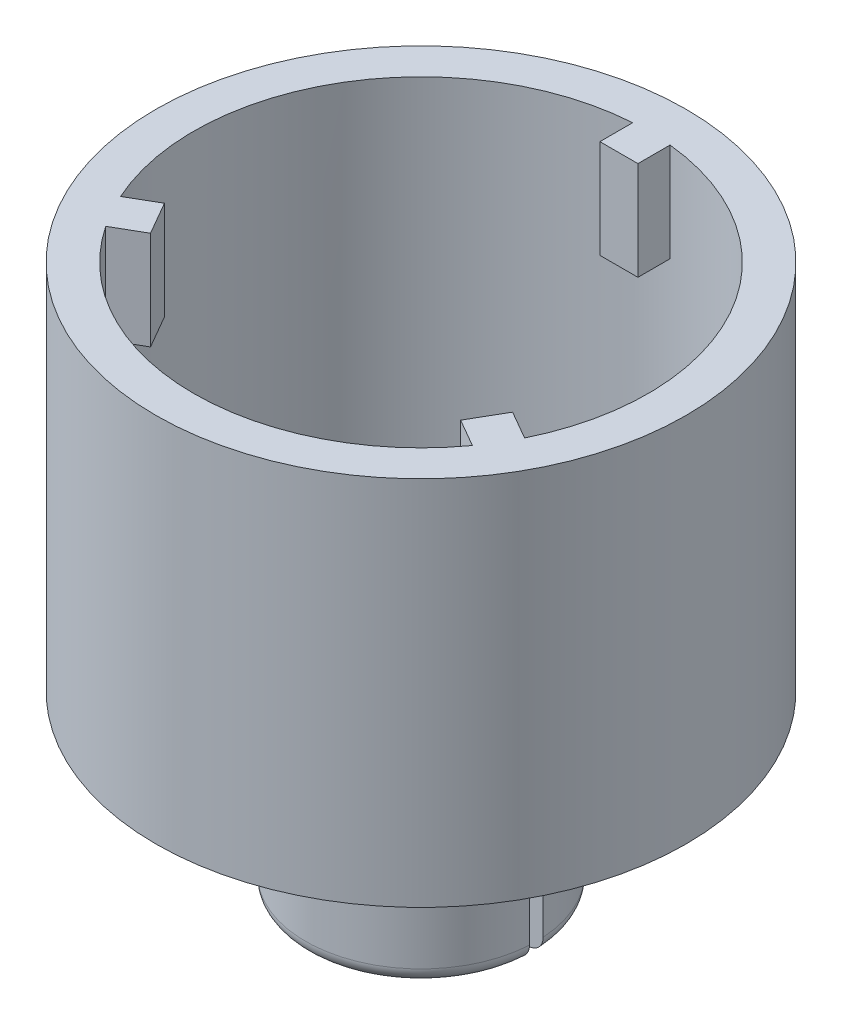
SolidWorks part; units mm, degrees
ref_plane "Front Plane" through (0, 0, 0) normal (0, 0, 1) x (1, 0, 0)
ref_plane "Top Plane" through (0, 0, 0) normal (0, 1, 0) x (1, 0, 0)
ref_plane "Right Plane" through (0, 0, 0) normal (1, 0, 0) x (0, 0, -1)
sketch "Sketch1" plane through (0, 0, 0) normal (0, 1, 0) x (1, 0, 0)
  circle A0 centre (0, 0) radius 35
  dimension "D1" = 70
extrude "Boss-Extrude1" add sketch "Sketch1" along normal blind 49
sketch "Sketch2" plane through (0, 49, 0) normal (0, 1, 0) x (1, 0, 0)
  circle A0 centre (0, 0) radius 30
  dimension "D1" = 60
extrude "Cut-Extrude1" cut sketch "Sketch2" against normal blind 46.9
sketch "Sketch3" plane through (0, 0, 0) normal (0, -1, 0) x (1, 0, 0)
  circle A0 centre (0, 0) radius 19.5
  dimension "D1" = 39
extrude "Boss-Extrude2" add sketch "Sketch3" along normal blind 7
sketch "Sketch4" plane through (0, -7, 0) normal (0, -1, 0) x (1, 0, 0)
  circle A0 centre (0, 0) radius 15.25
  dimension "D1" = 30.5
extrude "Boss-Extrude3" add sketch "Sketch4" along normal blind 16
fillet "Fillet1" radius 5 1 edges at (0, 0, -19.5)
sketch "Sketch5" plane through (0, 49, 0) normal (0, 1, 0) x (1, 0, 0)
  line L0 (-1.9905, 29.9339) -> (-1.9905, 25.6053)
  line L1 (-1.9905, 25.6053) -> (3.0302, 25.6053)
  line L2 (3.0302, 25.6053) -> (3.0302, 29.8466)
  line L3 (26.9188, -13.2431) -> (23.1701, -11.0788)
  line L4 (23.1701, -11.0788) -> (20.6597, -15.4269)
  line L5 (20.6597, -15.4269) -> (24.3328, -17.5475)
  line L6 (-24.9282, -16.6908) -> (-21.1796, -14.5265)
  line L7 (-21.1796, -14.5265) -> (-23.69, -10.1784)
  line L8 (-23.69, -10.1784) -> (-27.363, -12.299)
  circle A0 centre (0, 0) radius 30 construction
  arc A1 (24.3328, -17.5475) -> (26.9188, -13.2431) centre (0, 0) ccw
  circle A2 centre (0, 0) radius 30
  arc A3 (3.0302, 29.8466) -> (-1.9905, 29.9339) centre (0, 0) ccw
  arc A4 (-27.363, -12.299) -> (-24.9282, -16.6908) centre (0, 0) ccw
  point P19 (0, 0)
  dimension "D1" = 0
  dimension "D2" = 3
extrude "Boss-Extrude4" add sketch "Sketch5" against normal blind 13
sketch "Sketch7" plane through (0, -23, 0) normal (0, -1, 0) x (1, 0, 0)
  line L1 (33.0968, 0.9034) -> (-33.0968, 0.9034)
  line L2 (33.0968, 0.9034) -> (33.0968, -0.9034)
  line L3 (33.0968, -0.9034) -> (-33.0968, -0.9034)
  line L4 (-33.0968, 0.9034) -> (-33.0968, -0.9034)
  line L5 (33.0968, 0.9034) -> (-33.0968, -0.9034) construction
  line L6 (33.0968, -0.9034) -> (-33.0968, 0.9034) construction
  point P0 (0, 0)
extrude "Cut-Extrude2" cut sketch "Sketch7" against normal up to surface (16 mm away) up to face at (0, -7, -15.25)
fillet "Fillet2" radius 2 2 edges at (0, -23, 15.25) (0, -23, -15.25)
sketch "Sketch8" plane through (0, 2.1, 0) normal (0, 1, 0) x (1, 0, 0)
  circle A0 centre (0, 0) radius 10.3601
